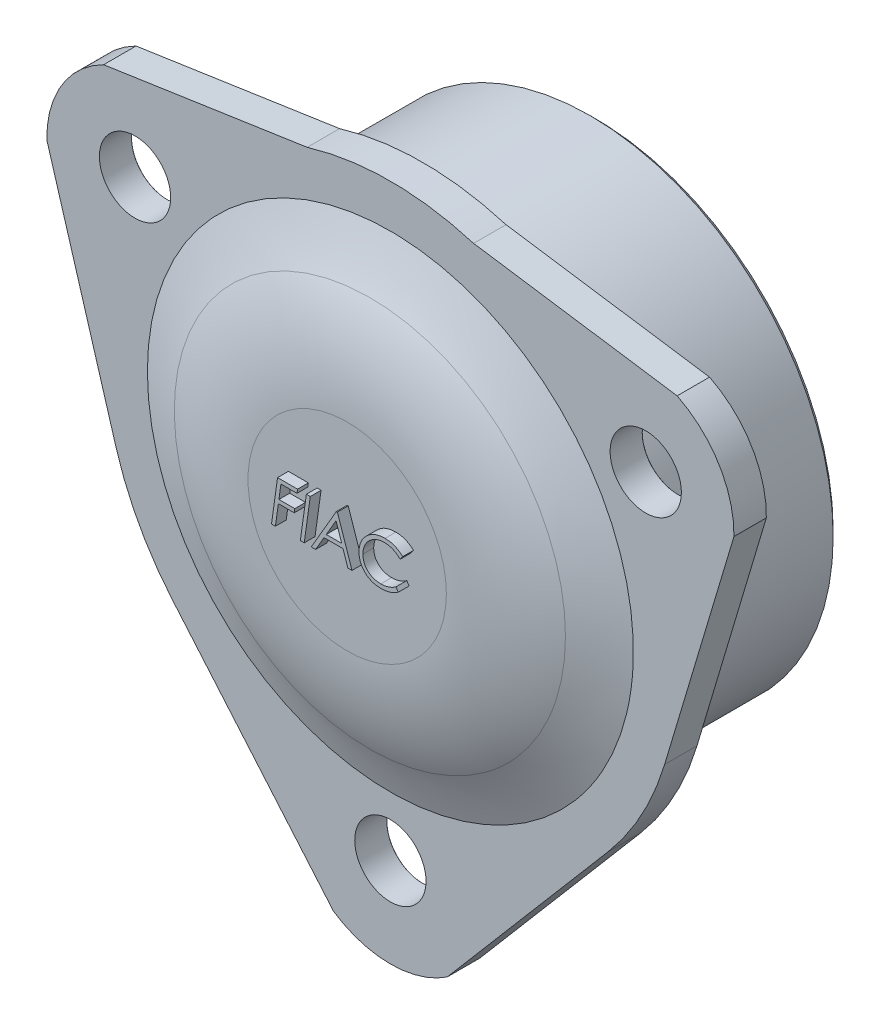
SolidWorks part; units mm, degrees
material "Lega 1060"
ref_plane "Piano frontale" through (0, 0, 0) normal (0, 0, 1) x (1, 0, 0)
ref_plane "Piano superiore" through (0, 0, 0) normal (0, 1, 0) x (1, 0, 0)
ref_plane "Piano destro" through (0, 0, 0) normal (1, 0, 0) x (0, 0, -1)
sketch "Schizzo2" plane through (0, 0, 0) normal (0, 0, 1) x (1, 0, 0)
  line L6 (31.8116, 90.4006) -> (25.3906, 68.9128)
  line L7 (5.2593, 41.8057) -> (20.1742, 59.3171)
  line L8 (-5.2593, 41.8057) -> (-20.1742, 59.3171)
  line L9 (-31.8116, 90.4006) -> (-25.3906, 68.9128)
  line L10 (-26.5523, 99.0547) -> (-7.705, 101.8551)
  line L11 (26.5523, 99.0547) -> (7.705, 101.8551)
  arc A10 (20.1742, 59.3171) -> (25.3906, 68.9128) centre (0, 76.5) ccw
  arc A11 (21.5, 61.0081) -> (25.3906, 68.9128) centre (0, 76.5) ccw
  arc A12 (-5.2593, 41.8057) -> (5.2593, 41.8057) centre (0, 49.7171) ccw
  arc A13 (-25.3906, 68.9128) -> (-20.1742, 59.3171) centre (0, 76.5) ccw
  arc A14 (-26.5523, 99.0547) -> (-31.8116, 90.4006) centre (-22.3129, 90.5531) ccw
  arc A15 (7.705, 101.8551) -> (-7.705, 101.8551) centre (0, 76.5) ccw
  arc A16 (1.5, 102.9575) -> (-7.705, 101.8551) centre (0, 76.5) ccw
  arc A17 (31.8116, 90.4006) -> (26.5523, 99.0547) centre (22.3129, 90.5531) ccw
  point P14 (23.6432, 91.5)
  point P19 (-23.6432, 91.5)
  point P24 (0, 48.5)
extrude "Estrusione-Estrusione2" add sketch "Schizzo2" along normal blind 3 contours L9 A13 L8 A12 L7 A10 L6 A17 L11 A15 L10 A14
ref_plane "Piano2" through (0, 0, 7) normal (0, 0, 1) x (1, 0, 0)
sketch "Schizzo4" plane through (0, 0, 7) normal (0, 0, 1) x (1, 0, 0)
  circle A0 centre (0, 76.5) radius 15
  point P0 (0, 76.5)
  dimension "D1" = 30
sketch "Schizzo5" plane through (0, 0, 3) normal (0, 0, 1) x (1, 0, 0)
  circle A0 centre (0, 76.5) radius 22.5
  dimension "D1" = 45
loft "Loft1" add profiles "Schizzo5", "Schizzo4" connector at (-20.9459, 84.717, 3) connector at (-8.2432, 89.0319, 7)
fillet "Raccordo1" radius 20 1 edges at (15, 76.5, 7)
hole_wizard "Foro per Vite M6-1" positions "Schizzo10" profile "Schizzo11" hole size "M6" standard "ISO" end condition through all
sketch "Schizzo10" plane through (0, 0, 0) normal (0, 0, -1) x (-1, 0, 0)
  point P0 (-23.6432, 91.5)
  point P3 (23.6432, 91.5)
  point P6 (0, 48.5)
sketch "Schizzo11" plane through (23.6432, 91.5, 0) normal (1, 0, 0) x (0, 1, 0)
  line L0 (0, 0) -> (0, 7)
  line L1 (0, 7) -> (3.3, 7)
  line L2 (3.3, 7) -> (3.3, 0.025)
  line L3 (3.3, 0.025) -> (3.325, 0)
  line L5 (3.325, 0) -> (0, 0)
  line L6 (-3.3, 0.025) -> (-3.325, 0) construction
  line L11 (0, -6.35) -> (0, 107.95) construction
  dimension "Thru Hole Dia." = 6.6
  dimension "Thru Hole Depth" = 7
  dimension "Near C'Sink Dia." = 6.65
  dimension "Near C'Sink Angle" = 90
sketch "Schizzo12" plane through (0, 0, 7) normal (0, 0, 1) x (1, 0, 0)
  line L0 (-6.109, 75) -> (6.109, 75) construction
  text T0 "<i>FIAC</i>" font "Century Gothic" height 4
  point P2 (0, 75)
  dimension "D1" = 1.5
extrude "Estrusione-Estrusione4" add sketch "Schizzo12" along normal blind 1
sketch "Schizzo13" plane through (0, 0, 0) normal (0, 0, -1) x (-1, 0, 0)
  circle A0 centre (0, 76.5) radius 22.5
  circle A1 centre (0, 76.5) radius 20
  dimension "D1" = 45
  dimension "D2" = 40
extrude "Estrusione-Estrusione5" add sketch "Schizzo13" along normal blind 16
chamfer "Smusso1" distance 0.5 angle 45 2 edges at (-20, 76.5, -16) (-22.5, 76.5, -16)
sketch "Schizzo14" plane through (0, 0, 0) normal (0, 0, -1) x (-1, 0, 0)
  circle A0 centre (0, 76.5) radius 20 construction
  circle A1 centre (0, 76.5) radius 20
  circle A2 centre (0, 76.5) radius 17
  dimension "D1" = 3
extrude "Estrusione-Estrusione6" add sketch "Schizzo14" along normal blind 4
chamfer "Smusso2" distance 0.5 angle 45 1 edges at (-17, 76.5, -4)
